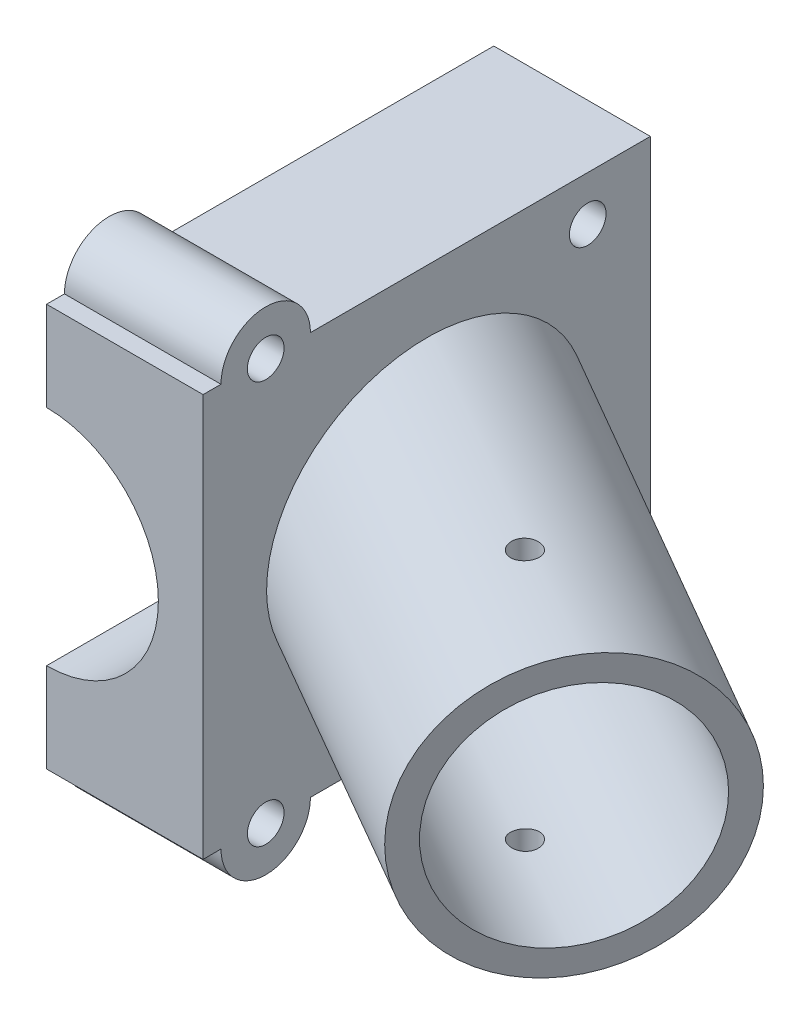
SolidWorks part; units mm, degrees
material "PLA"
ref_plane "Front Plane" through (0, 0, 0) normal (0, 0, 1) x (1, 0, 0)
ref_plane "Top Plane" through (0, 0, 0) normal (0, 1, 0) x (1, 0, 0)
ref_plane "Right Plane" through (0, 0, 0) normal (1, 0, 0) x (0, 0, -1)
sketch "Sketch1" plane through (0, 0, 0) normal (0, 0, 1) x (1, 0, 0)
  line L0 (-17.5, 22.5) -> (-17.5, 0)
  line L1 (55, 0) -> (-55, 0) construction
  line L2 (-17.5, 0) -> (17.5, 0)
  line L3 (17.5, 0) -> (17.5, 22.5)
  line L4 (-17.5, 22.5) -> (-12.5, 22.5)
  line L5 (17.5, 22.5) -> (12.5, 22.5)
  line L6 (0, -44.7868) -> (0, 44.7868) construction
  arc A0 (-12.5, 22.5) -> (12.5, 22.5) centre (0, 22.5) ccw
  dimension "D1" = 12.5
  dimension "D2" = 22.5
  dimension "D3" = 5
extrude "Boss-Extrude1" add sketch "Sketch1" along normal mid plane 50
sketch "Construct1" plane through (0, 0, 0) normal (0, 1, 0) x (1, 0, 0)
  line L0 (17.5, 0) -> (43.4808, -15) construction
  line L1 (-44.2539, 0) -> (44.2539, 0) construction
  line L2 (34.7051, -0.1998) -> (26.2756, -14.8002) construction
  line L3 (17.5, -25) -> (17.5, 25) construction
  point P6 (30.4904, -7.5)
  point P7 (30.4904, -7.5)
  dimension "D1" = 30
  dimension "D2" = 15
ref_plane "LegBuildPlane" through (26.1154, 0, 15.0777) normal (0.866, 0, 0.5) x (0.5, 0, -0.866)
sketch "Sketch5" plane through (26.1154, 0, 15.0777) normal (0.866, 0, 0.5) x (0.5, 0, -0.866)
  line L0 (-6.75, 22.5) -> (-3.9, 22.5)
  line L1 (21.4, 22.5) -> (24.25, 22.5)
  line L2 (17.1795, 0) -> (0.3205, 0) construction
  arc A0 (-3.9, 22.5) -> (21.4, 22.5) centre (8.75, 22.5) ccw
  arc A1 (-6.75, 22.5) -> (24.25, 22.5) centre (8.75, 22.5) ccw
  point P9 (8.75, 0)
  dimension "D1" = 15.5
  dimension "D2" = 12.65
  dimension "D3" = 22.5
  dimension "D4" = 0
extrude "Boss-Extrude2" add sketch "Sketch5" against normal up to surface and the other way blind 30 up to face at (17.5, 11.25, 0)
sketch "Sketch9" plane through (-17.5, 0, 0) normal (-1, 0, 0) x (0, 0, 1)
  line L2 (55, 0) -> (-55, 0) construction
  line L3 (-25, 22.5) -> (-25, 0) construction
  circle A0 centre (-18, 5) radius 2.05
  dimension "D3" = 5
  dimension "D1" = 4.1
  dimension "D4" = 7
extrude "Cut-Extrude3" cut sketch "Sketch9" against normal up to surface (35 mm away) up to face at (17.5, 12.4167, 0)
sketch "Construct2" plane through (0, 22.5, 0) normal (0, 1, 0) x (1, 0, 0)
  line L0 (20.0981, -16.107) -> (32.7481, 5.8035) construction
  line L2 (50.1461, -33.4552) -> (17.5, -14.607) construction
  line L3 (62.7961, -11.5448) -> (17.5, 14.607) construction
  line L4 (17.5, 0) -> (26.4231, -5.1517) construction
  line L11 (-44.2539, 0) -> (44.2539, 0) construction
  dimension "D1" = 3
  dimension "D2" = 90
ref_plane "LegBuildPlane2" through (22.0481, 0, 12.7295) normal (0.866, 0, 0.5) x (0.5, 0, -0.866)
sketch "Sketch12" plane through (22.0481, 0, 12.7295) normal (0.866, 0, 0.5) x (0.5, 0, -0.866)
  line L0 (-3.9, 22.5) -> (21.4, 22.5)
  arc A0 (-3.9, 22.5) -> (21.4, 22.5) centre (8.75, 22.5) ccw
extrude "Boss-Extrude5" add sketch "Sketch12" against normal up to surface (17.607 mm away) up to face at (17.5, 16.175, 0)
mirror "Mirror1" about plane through (17.5, 22.5, 25) normal (0, -1, 0) of "Boss-Extrude2", "Boss-Extrude1", "Cut-Extrude3", "Boss-Extrude5"
sketch "Sketch13" plane through (0, 0, 0) normal (0, 1, 0) x (1, 0, 0)
  line L0 (17.5, 0) -> (43.4808, -15) construction
  line L1 (48.7211, -35.9234) -> (64.2211, -9.0766) construction
  circle A0 centre (43.4808, -15) radius 1.55
  dimension "D2" = 3.1
  dimension "D1" = 15
extrude "Cut-Extrude4" cut sketch "Sketch13" along normal through all
sketch "Sketch16" plane through (0, 0, 0) normal (1, 0, 0) x (0, 0, -1)
  line L0 (55, 0) -> (-55, 0) construction
  line L1 (25, 45) -> (-25, 45)
  line L2 (25, 45) -> (25, 0)
  line L3 (25, 0) -> (-25, 0)
  line L4 (-25, 45) -> (-25, 0)
  line L5 (-25, 45) -> (-25, 0) construction
extrude "Cut-Extrude5" cut sketch "Sketch16" against normal up to surface (17.5 mm away) up to face at (-17.5, 40, -15.95)
sketch "Sketch18" plane through (0, 0, 0) normal (-1, 0, 0) x (0, 0, 1)
  line L0 (55, 0) -> (-55, 0) construction
  line L2 (13, 0) -> (23, 0)
  arc A0 (23, 0) -> (13, 0) centre (18, 0) cw
  circle A3 centre (-18, 5) radius 2.05 construction
  dimension "D3" = 5
  dimension "D1" = 36
extrude "Boss-Extrude6" add sketch "Sketch18" against normal blind 17.5
sketch "Sketch20" plane through (0, 0, 0) normal (-1, 0, 0) x (0, 0, 1)
  circle A0 centre (18, 0) radius 2.05
  dimension "D1" = 4.1
extrude "Cut-Extrude6" cut sketch "Sketch20" against normal up to surface (17.5 mm away) up to face at (17.5, 40, -15.95)
ref_plane "HolePlane" through (0, 22.5, 0) normal (0, 1, 0) x (1, 0, 0)
mirror "Mirror2" about plane through (0, 22.5, 0) normal (0, 1, 0) of "Boss-Extrude6", "Cut-Extrude6"
equation "\"TubeDiam\"=12.5"
equation "\"D1@Sketch1\"=\"TubeDiam\""
equation "\"D2@Sketch1\"=\"ClampHeight\""
equation "\"MountLength\"= 50"
equation "\"D1@Boss-Extrude1\"=\"MountLength\""
equation "\"MountHoleSize\"=3.1"
equation "\"LipWidth\"= 5"
equation "\"D3@Sketch1\"=\"LipWidth\""
equation "\"LegDiam\"= 12.5"
equation "\"LegThickness\"= \"TubeDiam\" + 3"
equation "\"D1@Sketch5\"=\"LegThickness\""
equation "\"ClampHeight\"= \"TubeDiam\" + 10"
equation "\"D3@Sketch5\"=\"ClampHeight\""
equation "\"HubHoleDist\"=7"
equation "\"HubHoleSize\"=4.1"
equation "\"D2@Sketch13\"=\"MountHoleSize\""
equation "\"D1@Sketch9\"=\"HubHoleSize\""
equation "\"D4@Sketch9\"=\"HubHoleDist\""
equation "\"D1@Sketch18\"=\"MountLength\" - 2 * \"HubHoleDist\""
equation "\"D1@Boss-Extrude6\"=\"TubeDiam\" +5"
equation "\"D1@Sketch20\"=\"HubHoleSize\""
